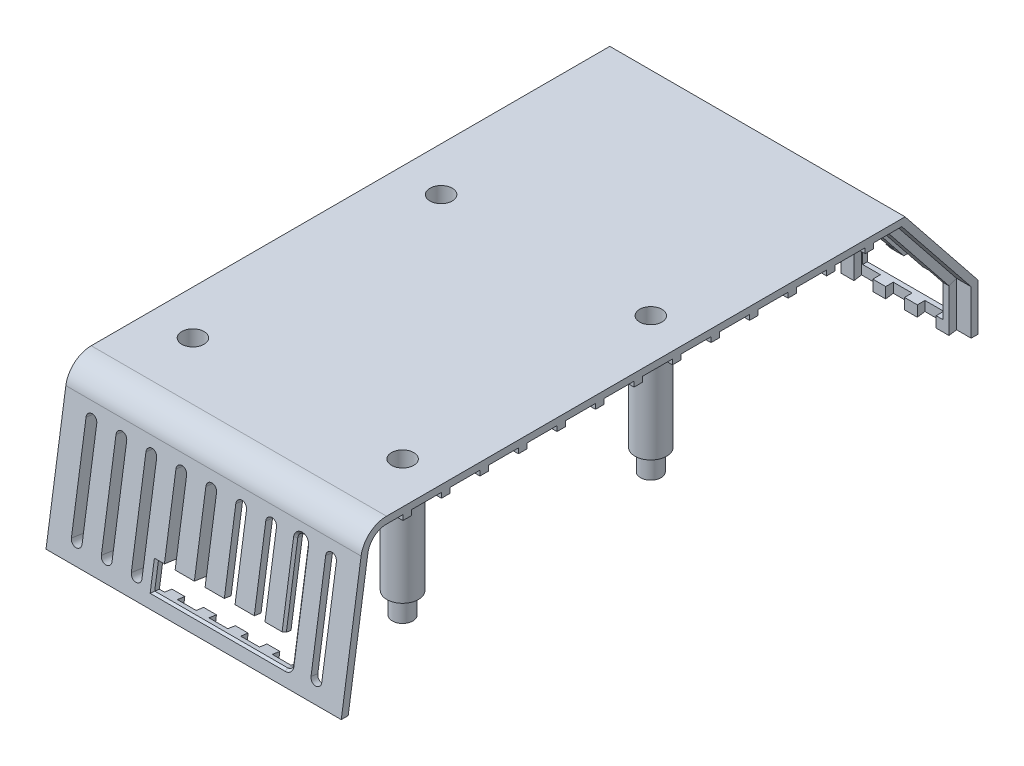
SolidWorks part; units mm, degrees
material "PPS"
ref_plane "前视基准面" through (0, 0, 0) normal (0, 0, 1) x (1, 0, 0)
ref_plane "上视基准面" through (0, 0, 0) normal (0, 1, 0) x (1, 0, 0)
ref_plane "右视基准面" through (0, 0, 0) normal (1, 0, 0) x (0, 0, -1)
sketch "草图2" plane through (0, 0, 0) normal (1, 0, 0) x (0, 0, -1)
  line L32 (-2.0016, 6.75) -> (-2.0016, 17.1644)
  line L33 (-2.0016, 17.1644) -> (-18.214, 37.4471)
  line L34 (-18.214, 37.4471) -> (-138.6289, 37.4471)
  line L35 (-142.9799, 33.7021) -> (-147.0375, 6.75)
  line L36 (0, 0) -> (-169.6172, 0) construction
  line L38 (-17.4446, 39.0471) -> (-138.6289, 39.0471)
  line L39 (-144.5621, 33.9403) -> (-148.6556, 6.75)
  line L40 (-0.4016, 6.75) -> (-0.4016, 17.7253)
  line L41 (-0.4016, 17.7253) -> (-17.4446, 39.0471)
  line L42 (-147.0375, 6.75) -> (-148.6556, 6.75) construction
  line L43 (-142.9799, 33.7021) -> (-147.9563, 0.6471) construction
  line L44 (-147.9563, 0.6471) -> (-2.0016, 0.6471) construction
  line L45 (-149.8153, -0.9529) -> (-0.4016, -0.9529) construction
  line L46 (-144.5621, 33.9403) -> (-149.8153, -0.9529) construction
  line L47 (-0.4016, -0.9529) -> (-0.4016, 17.7253) construction
  line L48 (-2.0016, 0.6471) -> (-2.0016, 17.1644) construction
  line L49 (-2.0016, 6.75) -> (-0.4016, 6.75)
  line L50 (-148.6556, 6.75) -> (-149.1976, 3.15)
  line L51 (-149.1976, 3.15) -> (-147.5795, 3.15)
  line L52 (-147.5795, 3.15) -> (-147.0375, 6.75)
  arc A4 (-138.6289, 39.0471) -> (-144.5621, 33.9403) centre (-138.6289, 33.0471) ccw
  arc A5 (-138.6289, 37.4471) -> (-142.9799, 33.7021) centre (-138.6289, 33.0471) ccw
  dimension "D1" = 1.6
  dimension "D3" = 6
  dimension "D2" = 6.75
  dimension "D4" = 3.15
extrude "凸台-拉伸1" add sketch "草图2" along normal blind 69
sketch "草图7" plane through (0, 3.15, 0) normal (0, -1, 0) x (1, 0, 0)
  line L1 (33, 147.58) -> (33, 145.78)
  line L2 (33, 145.78) -> (36, 145.78)
  line L3 (36, 145.78) -> (36, 147.58)
  line L28 (28.6, 145.78) -> (28.6, 147.58)
  line L29 (25.6, 145.78) -> (28.6, 145.78)
  line L30 (25.6, 147.58) -> (25.6, 145.78)
  line L31 (21.2, 145.78) -> (21.2, 147.58)
  line L32 (18.2, 145.78) -> (21.2, 145.78)
  line L33 (18.2, 147.58) -> (18.2, 145.78)
  line L34 (13.8, 145.78) -> (13.8, 147.58)
  line L35 (10.8, 145.78) -> (13.8, 145.78)
  line L36 (10.8, 147.58) -> (10.8, 145.78)
  line L37 (6.4, 145.78) -> (6.4, 147.58)
  line L38 (3.4, 145.78) -> (6.4, 145.78)
  line L39 (3.4, 147.58) -> (3.4, 145.78)
  line L40 (36, 145.78) -> (28.6, 145.78) construction
  line L41 (40.4, 147.58) -> (40.4, 145.78)
  line L42 (43.4, 145.78) -> (43.4, 147.58)
  line L43 (43.4, 147.58) -> (40.4, 147.58)
  line L44 (40.4, 145.78) -> (43.4, 145.78)
  line L45 (47.8, 147.58) -> (47.8, 145.78)
  line L46 (50.8, 145.78) -> (50.8, 147.58)
  line L47 (50.8, 147.58) -> (47.8, 147.58)
  line L48 (47.8, 145.78) -> (50.8, 145.78)
  line L49 (55.2, 147.58) -> (55.2, 145.78)
  line L50 (58.2, 145.78) -> (58.2, 147.58)
  line L51 (58.2, 147.58) -> (55.2, 147.58)
  line L52 (55.2, 145.78) -> (58.2, 145.78)
  line L53 (62.6, 147.58) -> (62.6, 145.78)
  line L54 (65.6, 145.78) -> (65.6, 147.58)
  line L55 (65.6, 147.58) -> (62.6, 147.58)
  line L56 (62.6, 145.78) -> (65.6, 145.78)
  line L57 (33, 147.58) -> (40.4, 147.58) construction
  line L58 (0, 147.5795) -> (0, 142.9799) construction
  line L103 (28.6, 147.58) -> (25.6, 147.58)
  line L104 (21.2, 147.58) -> (18.2, 147.58)
  line L105 (13.8, 147.58) -> (10.8, 147.58)
  line L106 (36, 147.58) -> (33, 147.58)
  line L107 (6.4, 147.58) -> (3.4, 147.58)
  dimension "D1" = 3
  dimension "D2" = 33
  dimension "D5" = 7.4
  dimension "D7" = 7.4
  dimension "D3" = 5
  dimension "D4" = 1
  dimension "D6" = 5
sketch "草图17" plane through (0, 0, 0) normal (-1, 0, 0) x (0, 0, 1)
  line L0 (147.5795, 3.15) -> (143.0568, 33.1914)
  line L1 (147.5795, 3.15) -> (142.9799, 33.7021) construction
  line L2 (138.1125, 37.4471) -> (18.214, 37.4471)
  line L3 (138.6289, 37.4471) -> (18.214, 37.4471) construction
  line L4 (149.1976, 3.15) -> (147.5795, 3.15) construction
  line L5 (18.214, 37.4471) -> (2.0016, 17.1644)
  line L6 (2.0016, 17.1644) -> (2.0016, 6.75)
  arc A0 (138.1125, 37.4471) -> (143.0568, 33.1914) centre (138.1125, 32.4471) cw
  dimension "D1" = 5
sweep "扫描1" add profiles "草图7" path "草图17"
sketch "草图18" plane through (0, 37.4471, 0) normal (0, -1, 0) x (1, 0, 0)
  line L0 (69, 0.4016) -> (0, 0.4016) construction
  line L1 (0, 17.4446) -> (0, 138.6289) construction
  circle A0 centre (59.3, 67.1616) radius 3.7
  circle A1 centre (59.3, 125.1616) radius 3.7
  circle A2 centre (10.3, 125.1616) radius 3.7
  circle A3 centre (10.3, 67.1616) radius 3.7
  dimension "D4" = 49
  dimension "D1" = 66.76
  dimension "D2" = 66.76
  dimension "D3" = 10.3
  dimension "D5" = 58
  dimension "D6" = 58
  dimension "D7" = 49
  dimension "D8" = 10.3
extrude "凸台-拉伸2" add sketch "草图18" along normal blind 30
sketch "草图28" plane through (69, 0, 0) normal (1, 0, 0) x (0, 0, -1)
  line L0 (-138.6289, 37.4471) -> (-18.214, 37.4471) construction
  line L1 (-132.7865, 37.4471) -> (-134.7865, 37.4471)
  line L2 (-132.7865, 37.4471) -> (-132.7865, 36.2471)
  line L3 (-132.7865, 36.2471) -> (-134.7865, 36.2471)
  line L4 (-134.7865, 37.4471) -> (-134.7865, 36.2471)
  line L5 (-123.7865, 37.4471) -> (-125.7865, 37.4471)
  line L6 (-123.7865, 37.4471) -> (-123.7865, 36.2471)
  line L7 (-123.7865, 36.2471) -> (-125.7865, 36.2471)
  line L8 (-125.7865, 37.4471) -> (-125.7865, 36.2471)
  line L9 (-114.7865, 37.4471) -> (-116.7865, 37.4471)
  line L10 (-114.7865, 37.4471) -> (-114.7865, 36.2471)
  line L11 (-114.7865, 36.2471) -> (-116.7865, 36.2471)
  line L12 (-116.7865, 37.4471) -> (-116.7865, 36.2471)
  line L13 (-105.7865, 37.4471) -> (-107.7865, 37.4471)
  line L14 (-105.7865, 37.4471) -> (-105.7865, 36.2471)
  line L15 (-105.7865, 36.2471) -> (-107.7865, 36.2471)
  line L16 (-107.7865, 37.4471) -> (-107.7865, 36.2471)
  line L17 (-96.7865, 37.4471) -> (-98.7865, 37.4471)
  line L18 (-96.7865, 37.4471) -> (-96.7865, 36.2471)
  line L19 (-96.7865, 36.2471) -> (-98.7865, 36.2471)
  line L20 (-98.7865, 37.4471) -> (-98.7865, 36.2471)
  line L21 (-87.7865, 37.4471) -> (-89.7865, 37.4471)
  line L22 (-87.7865, 37.4471) -> (-87.7865, 36.2471)
  line L23 (-87.7865, 36.2471) -> (-89.7865, 36.2471)
  line L24 (-89.7865, 37.4471) -> (-89.7865, 36.2471)
  line L25 (-78.7865, 37.4471) -> (-80.7865, 37.4471)
  line L26 (-78.7865, 37.4471) -> (-78.7865, 36.2471)
  line L27 (-78.7865, 36.2471) -> (-80.7865, 36.2471)
  line L28 (-80.7865, 37.4471) -> (-80.7865, 36.2471)
  line L29 (-69.7865, 37.4471) -> (-71.7865, 37.4471)
  line L30 (-69.7865, 37.4471) -> (-69.7865, 36.2471)
  line L31 (-69.7865, 36.2471) -> (-71.7865, 36.2471)
  line L32 (-71.7865, 37.4471) -> (-71.7865, 36.2471)
  line L33 (-60.7865, 37.4471) -> (-62.7865, 37.4471)
  line L34 (-60.7865, 37.4471) -> (-60.7865, 36.2471)
  line L35 (-60.7865, 36.2471) -> (-62.7865, 36.2471)
  line L36 (-62.7865, 37.4471) -> (-62.7865, 36.2471)
  line L37 (-51.7865, 37.4471) -> (-53.7865, 37.4471)
  line L38 (-51.7865, 37.4471) -> (-51.7865, 36.2471)
  line L39 (-51.7865, 36.2471) -> (-53.7865, 36.2471)
  line L40 (-53.7865, 37.4471) -> (-53.7865, 36.2471)
  line L41 (-42.7865, 37.4471) -> (-44.7865, 37.4471)
  line L42 (-42.7865, 37.4471) -> (-42.7865, 36.2471)
  line L43 (-42.7865, 36.2471) -> (-44.7865, 36.2471)
  line L44 (-44.7865, 37.4471) -> (-44.7865, 36.2471)
  line L45 (-33.7865, 37.4471) -> (-35.7865, 37.4471)
  line L46 (-33.7865, 37.4471) -> (-33.7865, 36.2471)
  line L47 (-33.7865, 36.2471) -> (-35.7865, 36.2471)
  line L48 (-35.7865, 37.4471) -> (-35.7865, 36.2471)
  line L49 (-24.7865, 37.4471) -> (-26.7865, 37.4471)
  line L50 (-24.7865, 37.4471) -> (-24.7865, 36.2471)
  line L51 (-24.7865, 36.2471) -> (-26.7865, 36.2471)
  line L52 (-26.7865, 37.4471) -> (-26.7865, 36.2471)
  dimension "D1" = 2
  dimension "D2" = 1.2
  dimension "D3" = 13
extrude "凸台-拉伸3" add sketch "草图28" against normal up to surface (69 mm away)
sketch "草图27" plane through (0, 39.0471, 0) normal (0, 1, 0) x (1, 0, 0)
  circle A0 centre (10.3, -67.1616) radius 2.6
  circle A1 centre (59.3, -125.1616) radius 2.6
  circle A2 centre (10.3, -125.1616) radius 2.6
  circle A3 centre (59.3, -67.1616) radius 2.6
extrude "切除-拉伸6" cut sketch "草图27" against normal blind 25
sketch "草图29" plane through (0, 7.4471, 0) normal (0, -1, 0) x (1, 0, 0)
  circle A0 centre (59.3, 67.1616) radius 1.35
  circle A1 centre (10.3, 67.1616) radius 1.35
  circle A2 centre (10.3, 125.1616) radius 1.35
  circle A3 centre (59.3, 125.1616) radius 1.35
extrude "切除-拉伸7" cut sketch "草图29" against normal up to next
sketch "草图30" plane through (0, 7.4471, 0) normal (0, -1, 0) x (1, 0, 0)
  circle A0 centre (59.3, 67.1616) radius 2.4
  circle A1 centre (59.3, 67.1616) radius 4
  circle A2 centre (10.3, 67.1616) radius 2.4
  circle A3 centre (10.3, 67.1616) radius 4
  circle A4 centre (10.3, 125.1616) radius 2.4
  circle A5 centre (10.3, 125.1616) radius 4
  circle A6 centre (59.3, 125.1616) radius 2.4
  circle A7 centre (59.3, 125.1616) radius 4
extrude "切除-拉伸8" cut sketch "草图30" against normal blind 5
sketch "草图31" plane through (0, 6.7142, -8.3998) normal (0, 0.6244, -0.7811) x (-1, 0, 0)
  text T0 "<b>X M U</b>" font "Century Gothic" height 12
extrude "切除-拉伸9" cut sketch "草图31" against normal up to next
sketch "草图32" plane through (0, 22.0337, 146.3546) normal (0, 0.1489, 0.9889) x (1, 0, 0)
  line L0 (34.5, 8.5) -> (34.5, -14.5) construction
  line L1 (35.75, 8.5) -> (35.75, -14.5)
  line L2 (33.25, 8.5) -> (33.25, -14.5)
  line L3 (41.5, 8.5) -> (41.5, -14.5) construction
  line L4 (42.75, 8.5) -> (42.75, -14.5)
  line L5 (40.25, 8.5) -> (40.25, -14.5)
  line L6 (48.5, 8.5) -> (48.5, -14.5) construction
  line L7 (49.75, 8.5) -> (49.75, -14.5)
  line L8 (47.25, 8.5) -> (47.25, -14.5)
  line L9 (55.5, 8.5) -> (55.5, -14.5) construction
  line L10 (56.75, 8.5) -> (56.75, -14.5)
  line L11 (54.25, 8.5) -> (54.25, -14.5)
  line L12 (62.5, 8.5) -> (62.5, -14.5) construction
  line L13 (63.75, 8.5) -> (63.75, -14.5)
  line L14 (61.25, 8.5) -> (61.25, -14.5)
  line L15 (27.5, 8.5) -> (27.5, -14.5) construction
  line L16 (28.75, 8.5) -> (28.75, -14.5)
  line L17 (26.25, 8.5) -> (26.25, -14.5)
  line L18 (20.5, 8.5) -> (20.5, -14.5) construction
  line L19 (21.75, 8.5) -> (21.75, -14.5)
  line L20 (19.25, 8.5) -> (19.25, -14.5)
  line L21 (13.5, 8.5) -> (13.5, -14.5) construction
  line L22 (14.75, 8.5) -> (14.75, -14.5)
  line L23 (12.25, 8.5) -> (12.25, -14.5)
  line L24 (6.5, 8.5) -> (6.5, -14.5) construction
  line L25 (7.75, 8.5) -> (7.75, -14.5)
  line L26 (5.25, 8.5) -> (5.25, -14.5)
  arc A0 (35.75, 8.5) -> (33.25, 8.5) centre (34.5, 8.5) ccw
  arc A1 (33.25, -14.5) -> (35.75, -14.5) centre (34.5, -14.5) ccw
  arc A2 (42.75, 8.5) -> (40.25, 8.5) centre (41.5, 8.5) ccw
  arc A3 (40.25, -14.5) -> (42.75, -14.5) centre (41.5, -14.5) ccw
  arc A4 (49.75, 8.5) -> (47.25, 8.5) centre (48.5, 8.5) ccw
  arc A5 (47.25, -14.5) -> (49.75, -14.5) centre (48.5, -14.5) ccw
  arc A6 (56.75, 8.5) -> (54.25, 8.5) centre (55.5, 8.5) ccw
  arc A7 (54.25, -14.5) -> (56.75, -14.5) centre (55.5, -14.5) ccw
  arc A8 (63.75, 8.5) -> (61.25, 8.5) centre (62.5, 8.5) ccw
  arc A9 (61.25, -14.5) -> (63.75, -14.5) centre (62.5, -14.5) ccw
  arc A10 (28.75, 8.5) -> (26.25, 8.5) centre (27.5, 8.5) ccw
  arc A11 (26.25, -14.5) -> (28.75, -14.5) centre (27.5, -14.5) ccw
  arc A12 (21.75, 8.5) -> (19.25, 8.5) centre (20.5, 8.5) ccw
  arc A13 (19.25, -14.5) -> (21.75, -14.5) centre (20.5, -14.5) ccw
  arc A14 (14.75, 8.5) -> (12.25, 8.5) centre (13.5, 8.5) ccw
  arc A15 (12.25, -14.5) -> (14.75, -14.5) centre (13.5, -14.5) ccw
  arc A16 (7.75, 8.5) -> (5.25, 8.5) centre (6.5, 8.5) ccw
  arc A17 (5.25, -14.5) -> (7.75, -14.5) centre (6.5, -14.5) ccw
  point P2 (34.5, -3)
  point P10 (41.5, -3)
  point P18 (48.5, -3)
  point P25 (55.5, -3)
  point P32 (62.5, -3)
  point P39 (27.5, -3)
  point P46 (20.5, -3)
  point P53 (13.5, -3)
  point P60 (6.5, -3)
  dimension "D1" = 5
  dimension "D3" = 4.5
  dimension "D4" = 4.5
  dimension "D2" = 5
extrude "切除-拉伸10" cut sketch "草图32" against normal up to next
sketch "草图33" plane through (0, 22.0337, 146.3546) normal (0, 0.1489, 0.9889) x (1, 0, 0)
  line L0 (24.4142, -15.75) -> (55.5, -15.75)
  line L1 (55.5, -15.75) -> (55.5, -9.55)
  line L2 (55.5, -9.55) -> (24.4142, -9.55)
  line L3 (24.4142, -9.55) -> (24.4142, -15.75)
  arc A3 (54.25, -14.5) -> (56.75, -14.5) centre (55.5, -14.5) ccw construction
extrude "切除-拉伸11" cut sketch "草图33" against normal up to next
sketch "草图34" plane through (0, 0, 0.4016) normal (0, 0, -1) x (-1, 0, 0)
  line L0 (-64.15, 9) -> (-64.15, 20.5)
  line L1 (-64.15, 20.5) -> (-43.65, 20.5)
  line L2 (-43.65, 20.5) -> (-43.65, 9)
  line L3 (-43.65, 9) -> (-64.15, 9)
  line L4 (-69, 6.75) -> (0, 6.75) construction
  dimension "D1" = 2.25
  dimension "D2" = 20.5
  dimension "D3" = 11.5
  dimension "D4" = 43.65
extrude "切除-拉伸12" cut sketch "草图34" against normal up to next
chamfer "倒角1" distance 0.5 angle 45 12 edges at (43.65, 13.3627, 0.4016) (53.9, 9, 0.4016) (64.15, 13.3627, 0.4016) (54.25, 21.5145, 146.4328) (55.5, 31.675, 144.9031) (56.75, 19.0671, 146.8012) (56.3839, 6.8212, 148.6449) (24.4142, 9.5246, 148.2379) (39.9571, 6.4592, 148.6994) (53.9, 20.5, 2.6195) (43.65, 19.1127, 1.5106) (64.15, 19.1127, 1.5106)
